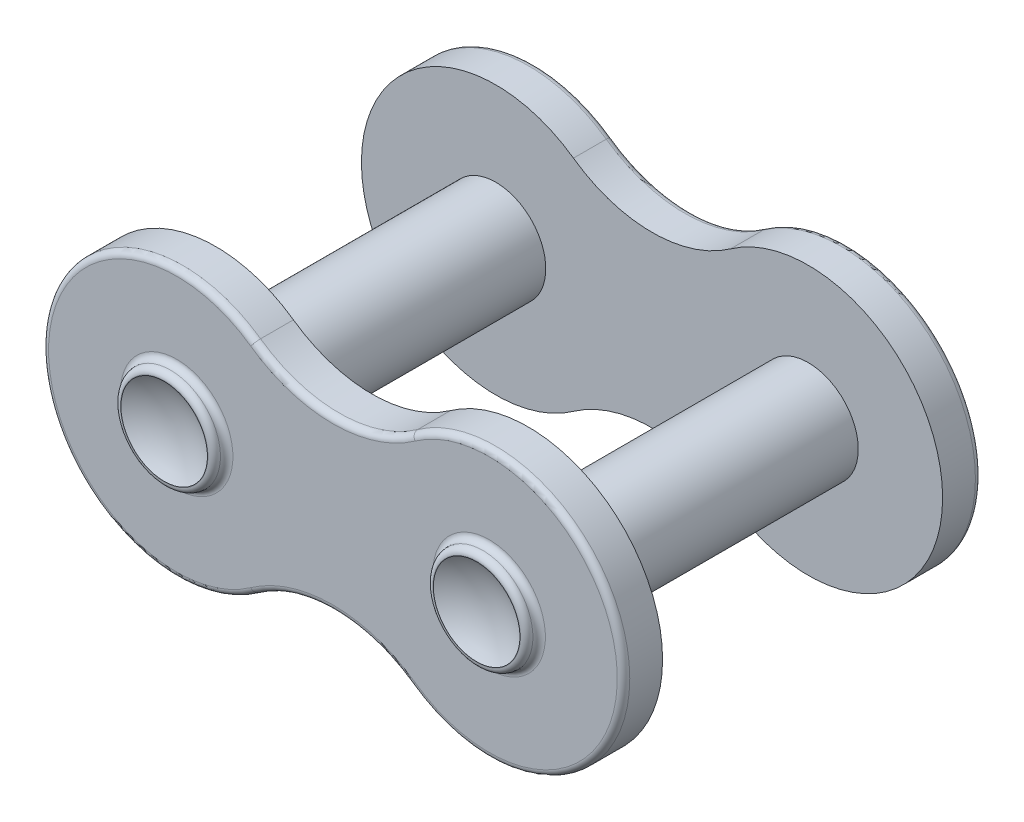
SolidWorks part; units mm, degrees
material "AISI 304"
ref_plane "Front Plane" through (0, 0, 0) normal (0, 0, 1) x (1, 0, 0)
ref_plane "Top Plane" through (0, 0, 0) normal (0, 1, 0) x (1, 0, 0)
ref_plane "Right Plane" through (0, 0, 0) normal (1, 0, 0) x (0, 0, -1)
sketch "Sketch1" plane through (0, 0, 0) normal (0, 0, 1) x (1, 0, 0)
  line L0 (0, 6.8052) -> (0, 3.4399) construction
  line L1 (-11.9667, 0) -> (9.7312, 0) construction
  line L2 (0, -3.4399) -> (0, -9.3695) construction
  arc A0 (3.1935, -4.4563) -> (3.1935, 4.4563) centre (6.35, 0) ccw
  circle A1 centre (6.35, 0) radius 2.032
  arc A2 (-3.1935, -4.4563) -> (-3.1935, 4.4563) centre (-6.35, 0) cw
  circle A3 centre (-6.35, 0) radius 2.032
  arc A4 (-3.1935, 4.4563) -> (3.1935, 4.4563) centre (0, 8.9649) ccw
  arc A5 (-3.1935, -4.4563) -> (3.1935, -4.4563) centre (0, -8.9649) cw
  dimension "D1" = 10.922
  dimension "D2" = 4.064
  dimension "D3" = 6.35
extrude "Boss-Extrude1" add sketch "Sketch1" along normal blind 1.5875
sketch "Sketch2" plane through (0, 0, 0) normal (0, 0, -1) x (-1, 0, 0)
  circle A0 centre (6.35, 0) radius 2.032 construction
  circle A1 centre (6.35, 0) radius 2.032
extrude "Boss-Extrude2" add sketch "Sketch2" against normal blind 15.0652 and the other way blind 0.508
ref_plane "Plane1" through (0, 0, 7.2786) normal (0, 0, -1) x (-1, 0, 0)
mirror "Mirror1" about plane through (0, 0, 7.2786) normal (0, 0, -1) of "Boss-Extrude1"
sketch "Sketch3" plane through (0, 0, 0) normal (0, 1, 0) x (1, 0, 0)
  line L0 (-6.35, -14.5572) -> (-6.35, -17.6857) construction
  line L1 (-8.382, -14.5572) -> (-4.318, -14.5572) construction
  line L2 (-6.35, -14.5572) -> (-6.35, -15.3798)
  line L3 (-6.35, -15.3798) -> (-8.5307, -15.3798)
  arc A0 (-6.35, -14.5572) -> (-8.5307, -15.3798) centre (-6.35, -17.8592) ccw
  dimension "D1" = 3.302
  dimension "D2" = 0.8225
revolve "Cut-Revolve1" cut sketch "Sketch3" angle 360 about L0
mirror "Mirror2" about plane through (0, 0, 0) normal (1, 0, 0) of "Cut-Revolve1", "Boss-Extrude2"
mirror "Mirror3" about plane through (0, 0, 7.2786) normal (0, 0, -1) of "Cut-Revolve1"
mirror "Mirror4" about plane through (0, 0, 0) normal (1, 0, 0) of "Mirror3"
fillet "Fillet1" radius 0.254 4 edges at (-8.382, 0, -0.508) (8.382, 0, -0.508) (8.382, 0, 15.0652) (-8.382, 0, 15.0652)
fillet "Fillet2" radius 0.254 12 edges at (-4.318, 0, 0) (8.382, 0, 0) (-11.811, 0, 0) (0, -3.4399, 0) (11.811, 0, 0) (0, 3.4399, 0) (11.811, 0, 14.5572) (0, -3.4399, 14.5572) (-11.811, 0, 14.5572) (0, 3.4399, 14.5572) (8.382, 0, 14.5572) (-8.382, 0, 14.5572)
